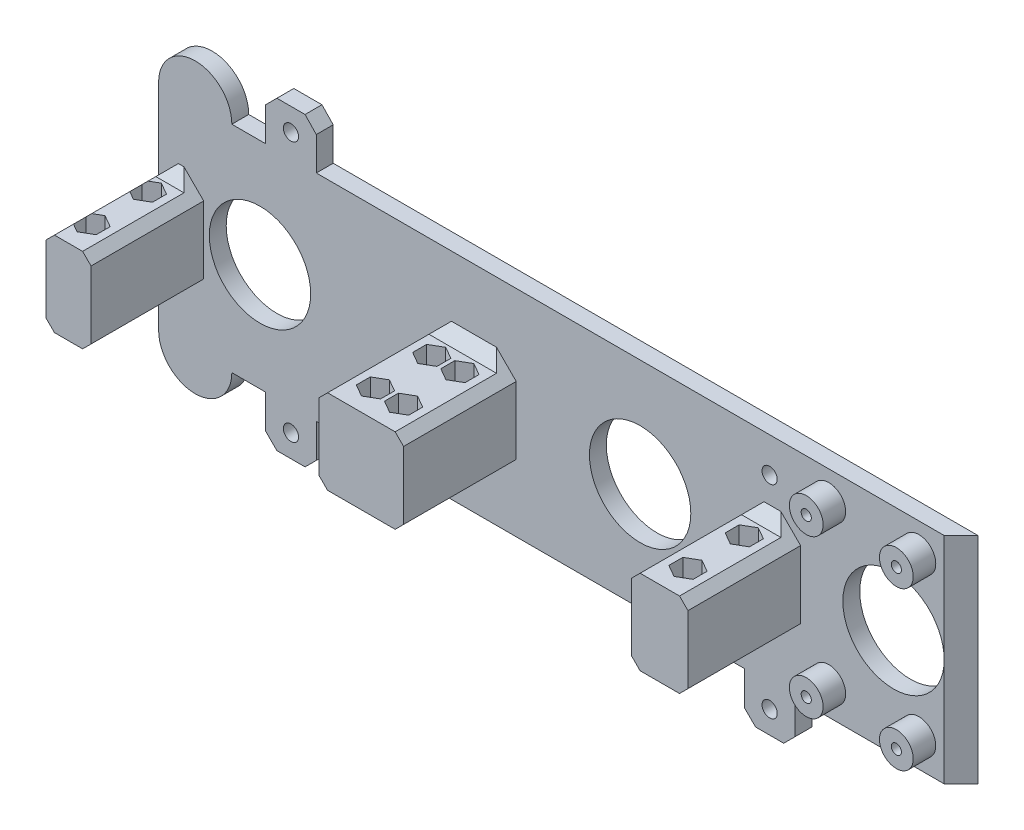
SolidWorks part; units mm, degrees
ref_plane "Front Plane" through (0, 0, 0) normal (0, 0, 1) x (1, 0, 0)
ref_plane "Top Plane" through (0, 0, 0) normal (0, 1, 0) x (1, 0, 0)
ref_plane "Right Plane" through (0, 0, 0) normal (1, 0, 0) x (0, 0, -1)
sketch "Sketch1" plane through (0, 0, 0) normal (0, 0, 1) x (1, 0, 0)
  line L0 (19, 38.2) -> (19, 44.2)
  line L1 (142.5, 38.2) -> (0, 38.2)
  line L2 (142.5, 38.2) -> (142.5, 0)
  line L3 (142.5, 0) -> (0, 0)
  line L4 (0, 38.2) -> (0, 0)
  line L5 (19, 44.2) -> (21, 46.2)
  line L6 (21, 46.2) -> (26, 46.2)
  line L7 (26, 46.2) -> (28, 44.1148)
  line L8 (28, 38.2) -> (28, 44.2) construction
  line L9 (28, 44.1148) -> (28, 38.2)
  line L10 (19, 0) -> (19, -6)
  line L11 (19, -6) -> (21, -8)
  line L12 (21, -8) -> (26, -8)
  line L13 (26, -8) -> (28, -6)
  line L14 (28, -6) -> (28, 0)
  line L15 (104, 0) -> (104, -6)
  line L16 (104, -6) -> (106, -8)
  line L17 (106, -8) -> (111, -8)
  line L18 (111, -8) -> (113, -6)
  line L19 (113, -6) -> (113, 0)
  arc A0 (0, 0) -> (13, 0) centre (6.5, 0) ccw
  arc A1 (0, 0) -> (13, 0) centre (6.5, 0) ccw construction
  arc A2 (0, 38.2) -> (13, 38.2) centre (6.5, 38.2) cw
  arc A3 (13, 38.2) -> (0, 38.2) centre (6.5, 38.2) ccw construction
  circle A4 centre (108.5, -4) radius 1.35
  circle A5 centre (23.5, -4) radius 1.35
  circle A6 centre (23.5, 42.2) radius 1.35
  circle A7 centre (108.5, 32) radius 1.35
extrude "Boss-Extrude1" add sketch "Sketch1" along normal blind 3 contours L1 L4 L3 L2 | A2 L1 | L3 A0 | L9 L7 L6 L5 L0 L1 A6 | L13 L14 L3 L10 L11 L12 A5 | L18 L19 L3 L15 L16 L17 A4 region at (19.1204, 41.2, 0) region at (71.2108, 19.0864, 0) region at (6.5, 40.9587, 0) region at (6.5, -2.7587, 0) region at (112.8796, -3, 0) region at (23.5, -0.1204, 0)
chamfer "Chamfer1" distance 3 angle 45 1 edges at (142.5, 19.1, 3)
sketch "Sketch2" plane through (0, 0, 0) normal (0, 0, -1) x (-1, 0, 0)
  circle A0 centre (-40.5, 19.1) radius 9
  circle A1 centre (-18, 19.1) radius 9
  circle A2 centre (-63, 19.1) radius 9
  circle A3 centre (-85.5, 19.1) radius 9
  circle A4 centre (-108, 19.1) radius 9
  circle A5 centre (-130.5, 19.1) radius 9
sketch "Sketch3" plane through (0, 0, 3) normal (0, 0, 1) x (1, 0, 0)
  line L0 (139.5, 38.2) -> (28, 38.2) construction
  line L1 (114, 10.4) -> (104, 10.4)
  line L2 (114, 10.4) -> (114, 25.4)
  line L3 (114, 25.4) -> (104, 25.4)
  line L4 (104, 10.4) -> (104, 25.4)
  line L5 (63.5, 10.4) -> (48.5, 10.4)
  line L6 (63.5, 10.4) -> (63.5, 25.4)
  line L7 (63.5, 25.4) -> (48.5, 25.4)
  line L8 (48.5, 10.4) -> (48.5, 25.4)
  line L9 (8, 10.4) -> (0, 10.4)
  line L10 (8, 10.4) -> (8, 25.4)
  line L11 (8, 25.4) -> (0, 25.4)
  line L12 (0, 10.4) -> (0, 25.4)
  line L13 (107.15, 32) -> (109.85, 32) construction
  line L14 (0, 38.2) -> (0, 0) construction
  circle A0 centre (108.5, 32) radius 1.35 construction
  point P19 (108.5, 32)
  dimension "D1" = 4.5
  dimension "D2" = 15
  dimension "D3" = 40.5
  dimension "D4" = 40.5
  dimension "D5" = 15
  dimension "D6" = 27.8
  dimension "D7" = 10
extrude "Boss-Extrude2" add sketch "Sketch3" along normal blind 20
sketch "Sketch4" plane through (0, 25.4, 0) normal (0, 1, 0) x (1, 0, 0)
  line L0 (48.5, -13) -> (63.5, -13) construction
  line L1 (48.5, -23) -> (48.5, -3) construction
  line L2 (63.5, -23) -> (63.5, -3) construction
  line L3 (104, -13) -> (114, -13) construction
  line L4 (104, -23) -> (104, -3) construction
  line L5 (114, -23) -> (114, -3) construction
  line L6 (8, -13) -> (0, -13) construction
  line L7 (8, -23) -> (8, -3) construction
  line L8 (0, -23) -> (0, -3) construction
  circle A0 centre (58.5, -18) radius 1.25
  circle A1 centre (53.5, -18) radius 1.25
  circle A2 centre (53.5, -8) radius 1.25
  circle A3 centre (58.5, -8) radius 1.25
  circle A4 centre (109, -18) radius 1.25
  circle A5 centre (3, -18) radius 1.25
  circle A6 centre (3, -8) radius 1.25
  circle A7 centre (109, -8) radius 1.25
  dimension "D2" = 2.5
  dimension "D1" = 5
  dimension "D3" = 5
  dimension "D4" = 5
  dimension "D5" = 5
  dimension "D6" = 5
extrude "Cut-Extrude1" cut sketch "Sketch4" against normal up to surface (15 mm away) up to face at (56, 10.4, 13)
chamfer "Chamfer2" distance 1.5 angle 45 12 edges at (0, 10.4, 13) (0, 25.4, 13) (114, 10.4, 13) (104, 10.4, 13) (63.5, 10.4, 13) (48.5, 10.4, 13) (8, 10.4, 13) (114, 25.4, 13) (104, 25.4, 13) (8, 25.4, 13) (63.5, 25.4, 13) (48.5, 25.4, 13)
sketch "Sketch5" plane through (0, 25.4, 0) normal (0, 1, 0) x (1, 0, 0)
  line L1 (3, -5.5174) -> (0.85, -6.7587)
  line L2 (0.85, -6.7587) -> (0.85, -9.2413)
  line L3 (0.85, -9.2413) -> (3, -10.4826)
  line L4 (3, -10.4826) -> (5.15, -9.2413)
  line L5 (5.15, -9.2413) -> (5.15, -6.7587)
  line L6 (5.15, -6.7587) -> (3, -5.5174)
  line L7 (3, -15.5174) -> (0.85, -16.7587)
  line L8 (0.85, -16.7587) -> (0.85, -19.2413)
  line L9 (0.85, -19.2413) -> (3, -20.4826)
  line L10 (3, -20.4826) -> (5.15, -19.2413)
  line L11 (5.15, -19.2413) -> (5.15, -16.7587)
  line L12 (5.15, -16.7587) -> (3, -15.5174)
  line L13 (53.5, -5.5174) -> (51.35, -6.7587)
  line L14 (51.35, -6.7587) -> (51.35, -9.2413)
  line L15 (51.35, -9.2413) -> (53.5, -10.4826)
  line L16 (53.5, -10.4826) -> (55.65, -9.2413)
  line L17 (55.65, -9.2413) -> (55.65, -6.7587)
  line L18 (55.65, -6.7587) -> (53.5, -5.5174)
  line L19 (58.5, -5.5174) -> (56.35, -6.7587)
  line L20 (56.35, -6.7587) -> (56.35, -9.2413)
  line L21 (56.35, -9.2413) -> (58.5, -10.4826)
  line L22 (58.5, -10.4826) -> (60.65, -9.2413)
  line L23 (60.65, -9.2413) -> (60.65, -6.7587)
  line L24 (60.65, -6.7587) -> (58.5, -5.5174)
  line L25 (58.5, -15.5174) -> (56.35, -16.7587)
  line L26 (56.35, -16.7587) -> (56.35, -19.2413)
  line L27 (56.35, -19.2413) -> (58.5, -20.4826)
  line L28 (58.5, -20.4826) -> (60.65, -19.2413)
  line L29 (60.65, -19.2413) -> (60.65, -16.7587)
  line L30 (60.65, -16.7587) -> (58.5, -15.5174)
  line L31 (53.5, -15.5174) -> (51.35, -16.7587)
  line L32 (51.35, -16.7587) -> (51.35, -19.2413)
  line L33 (51.35, -19.2413) -> (53.5, -20.4826)
  line L34 (53.5, -20.4826) -> (55.65, -19.2413)
  line L35 (55.65, -19.2413) -> (55.65, -16.7587)
  line L36 (55.65, -16.7587) -> (53.5, -15.5174)
  line L37 (109, -15.5174) -> (106.85, -16.7587)
  line L38 (106.85, -16.7587) -> (106.85, -19.2413)
  line L39 (106.85, -19.2413) -> (109, -20.4826)
  line L40 (109, -20.4826) -> (111.15, -19.2413)
  line L41 (111.15, -19.2413) -> (111.15, -16.7587)
  line L42 (111.15, -16.7587) -> (109, -15.5174)
  line L43 (109, -5.5174) -> (106.85, -6.7587)
  line L44 (106.85, -6.7587) -> (106.85, -9.2413)
  line L45 (106.85, -9.2413) -> (109, -10.4826)
  line L46 (109, -10.4826) -> (111.15, -9.2413)
  line L47 (111.15, -9.2413) -> (111.15, -6.7587)
  line L48 (111.15, -6.7587) -> (109, -5.5174)
  circle A0 centre (3, -8) radius 2.15 construction
  circle A1 centre (3, -18) radius 2.15 construction
  circle A2 centre (53.5, -8) radius 2.15 construction
  circle A3 centre (58.5, -8) radius 2.15 construction
  circle A4 centre (58.5, -18) radius 2.15 construction
  circle A5 centre (53.5, -18) radius 2.15 construction
  circle A6 centre (109, -18) radius 2.15 construction
  circle A7 centre (109, -8) radius 2.15 construction
  dimension "D1" = 4.3
extrude "Cut-Extrude2" cut sketch "Sketch5" against normal blind 8
extrude "Cut-Extrude3" cut sketch "Sketch2" against normal up to surface (3 mm away) contours A3 | A1 | A5 up to face at (56, 17.9, 3)
sketch "Sketch6" plane through (0, 0, 3) normal (0, 0, 1) x (1, 0, 0)
  line L0 (119, 0) -> (119, 38.2) construction
  line L1 (139.5, 0) -> (113, 0) construction
  line L2 (139.5, 38.2) -> (28, 38.2) construction
  line L3 (135, 38.2) -> (135, 0) construction
  line L4 (114, 11.9) -> (114, 23.9) construction
  line L5 (119, 19.1) -> (135, 19.1) construction
  circle A0 centre (119, 33.1) radius 3
  circle A1 centre (135, 33.1) radius 3
  circle A2 centre (135, 5.1) radius 3
  circle A3 centre (119, 5.1) radius 3
  dimension "D4" = 6
  dimension "D1" = 5
  dimension "D2" = 16
  dimension "D3" = 14
extrude "Boss-Extrude3" add sketch "Sketch6" along normal blind 4
sketch "Sketch7" plane through (0, 0, 7) normal (0, 0, 1) x (1, 0, 0)
  circle A0 centre (135, 33.1) radius 0.9
  circle A1 centre (119, 33.1) radius 0.9
  circle A2 centre (119, 5.1) radius 0.9
  circle A3 centre (135, 5.1) radius 0.9
  dimension "D1" = 1.8
extrude "Cut-Extrude4" cut sketch "Sketch7" against normal up to surface (7 mm away) up to face at (121.5, 19.1, 0)
chamfer "Chamfer3" distance 2 angle 45 3 edges at (4, 25.4, 3) (109, 25.4, 3) (56, 25.4, 3)
